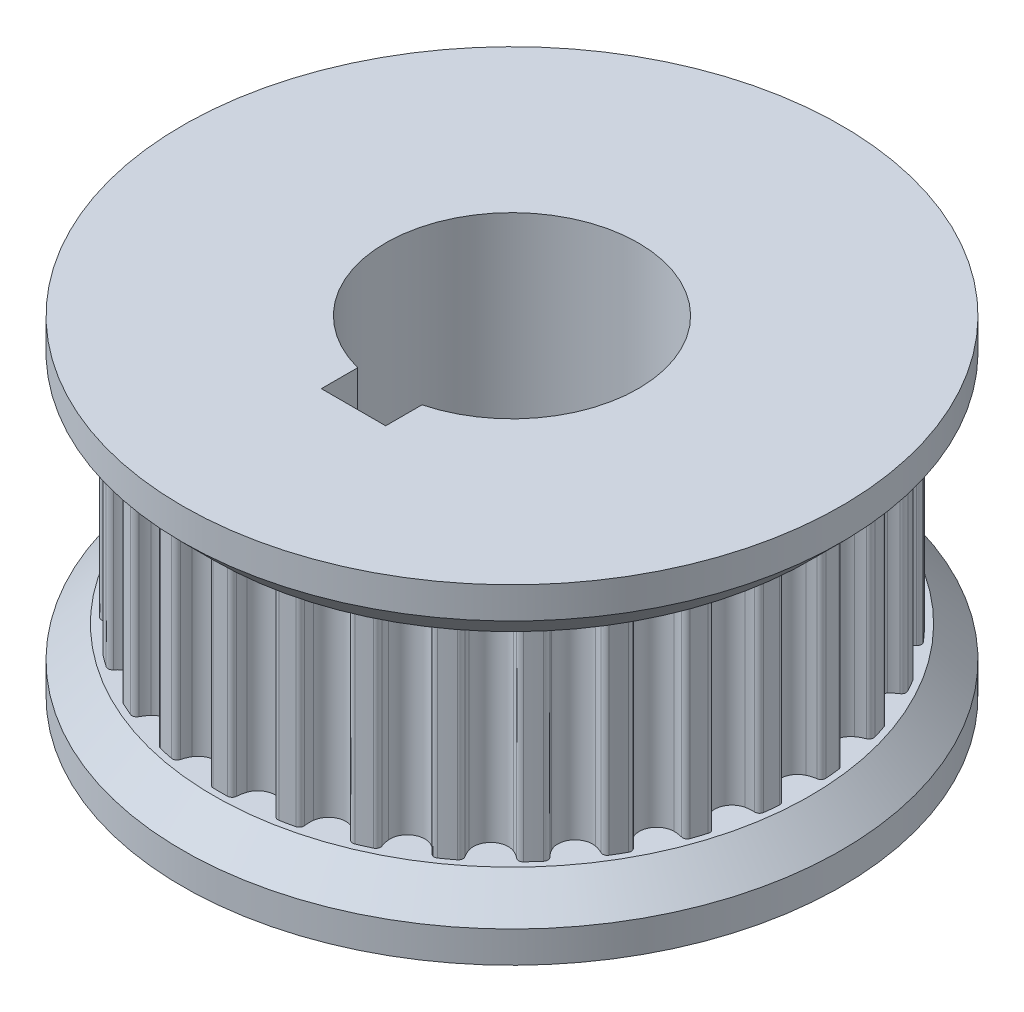
SolidWorks part; units mm, degrees
ref_plane "Plan de face" through (0, 0, 0) normal (0, 0, 1) x (1, 0, 0)
ref_plane "Plan de dessus" through (0, 0, 0) normal (0, 1, 0) x (1, 0, 0)
ref_plane "Plan de droite" through (0, 0, 0) normal (1, 0, 0) x (0, 0, -1)
sketch "Sketch1" plane through (0, 0, 0) normal (0, 1, 0) x (1, 0, 0)
  line L0 (0, 0) -> (0, 9.5493) construction
  line L1 (0, 0) -> (0.9982, 9.497) construction
  circle A0 centre (0, 0) radius 9.5493 construction
  circle A1 centre (0, 0) radius 9.2953 construction
  circle A2 centre (0, 0) radius 8.5453
  arc A3 (0.4257, 8.8722) -> (0.8932, 8.4985) centre (0.9512, 9.0504) ccw
  arc A4 (0.4257, 8.8722) -> (0.3736, 9.1492) centre (1.3727, 9.1934) cw
  arc A5 (-0.2275, 9.2925) -> (0.2275, 9.2925) centre (0, 0) cw
  arc A6 (0.2275, 9.2925) -> (0.3736, 9.1492) centre (0.2238, 9.1426) cw
  arc A7 (-0.4257, 8.8722) -> (-0.8932, 8.4985) centre (-0.9512, 9.0504) cw
  arc A8 (-0.4257, 8.8722) -> (-0.3736, 9.1492) centre (-1.3727, 9.1934) ccw
  arc A9 (-0.2275, 9.2925) -> (-0.3736, 9.1492) centre (-0.2238, 9.1426) ccw
  arc A10 (-0.8932, 8.4985) -> (0.8932, 8.4985) centre (0, 0) cw
  dimension "D2" = 18.5906
  dimension "D1" = 19.0986
  dimension "D6" = 0.555
  dimension "D5" = 17.0906
  dimension "D7" = 1
  dimension "D8" = 0.15
  dimension "D3" = 6
extrude "Boss-Extrude1" add sketch "Sketch1" against normal mid plane 6.5 contours A2
extrude "Boss-Extrude2" add sketch "Sketch1<5>" along normal mid plane 6.5 contours A4 A6 A5 A9 A8 A7 A10 A3
sketch "Sketch1<5>" plane through (0, 0, 0) normal (0, 1, 0) x (1, 0, 0) same geometry as "Sketch1"
pattern_circular "CirPattern1" count 30 every 12 about axis through (0, -3.25, 0) along (0, 1, 0) of "Boss-Extrude2" reverse direction yes
sketch "Sketch2" plane through (0, 3.25, 0) normal (0, 1, 0) x (1, 0, 0)
  circle A0 centre (0, 0) radius 10.5
  dimension "D1" = 21
extrude "Boss-Extrude4" add sketch "Sketch2" along normal blind 2 contours A0
sketch "Sketch3" plane through (0, -3.25, 0) normal (0, -1, 0) x (1, 0, 0)
  circle A0 centre (0, 0) radius 10.5
  circle A1 centre (0, 0) radius 10.5 construction
extrude "Boss-Extrude5" add sketch "Sketch3" along normal blind 2
chamfer "Chamfer1" distance 1 angle 45 2 edges at (0, -3.25, -10.5) (0, 3.25, 10.5)
sketch "Sketch4" plane through (0, -5.25, 0) normal (0, -1, 0) x (1, 0, 0)
  line L1 (-1.025, 5.05) -> (1.025, 5.05)
  line L2 (-1.025, 5.05) -> (-1.025, 3)
  line L3 (-1.025, 3) -> (1.025, 3)
  line L4 (1.025, 5.05) -> (1.025, 3)
  line L5 (-1.025, 5.05) -> (1.025, 3) construction
  line L6 (-1.025, 3) -> (1.025, 5.05) construction
  circle A0 centre (0, 0) radius 4.025
  point P3 (0, 4.025)
  dimension "D1" = 8.05
  dimension "D2" = 2.05
  dimension "D3" = 2.05
extrude "Cut-Extrude1" cut sketch "Sketch4" against normal through all contours L2 A0 L4 L3 | A0 L4 L1 L2 | L4 A0 L2 L3 region at (0, -5.25, 4.5148) region at (0, -5.25, 3.4913) region at (0, -5.25, -0.1436)
equation "\"NumTeeth\"= 30"
equation "\"ToothPitch\"= 2mm"
equation "\"PulleyDia\"= \"NumTeeth\" * \"ToothPitch\" / 3.1415926536"
equation "\"ToothAngle\"= 360deg / \"NumTeeth\" * 1deg"
equation "\"TransOffsetAngle\"= \"ToothAngle\" / 5 + 0.001"
equation "\"ShoulderRadius\"= 0.15mm"
equation "\"RootRadius\"= 0.555mm"
equation "\"TransRadius\"= 1mm"
equation "\"PLD\"= 0.254mm"
equation "\"PulleyThickness\"= 6.5"
equation "\"TransOffsetDia\"= \"PulleyDia\" - 0.254 * 2"
equation "\"D1@Sketch1\"=\"PulleyDia\""
equation "\"D2@Sketch1\"=\"TransOffsetDia\""
equation "\"ToothBottomDia\"= \"TransOffsetDia\" - 0.75 * 2"
equation "\"D5@Sketch1\"=\"ToothBottomDia\""
equation "\"D3@Sketch1\"=\"ToothAngle\"/2"
equation "\"D6@Sketch1\"=\"RootRadius\""
equation "\"D7@Sketch1\"=\"TransRadius\""
equation "\"D8@Sketch1\"=\"ShoulderRadius\""
equation "\"D1@Boss-Extrude1\"=\"PulleyThickness\""
equation "\"D2@CirPattern1\"=\"ToothAngle\""
equation "\"D1@CirPattern1\"=\"NumTeeth\""
equation "\"D1@Boss-Extrude2\"=\"PulleyThickness\""
